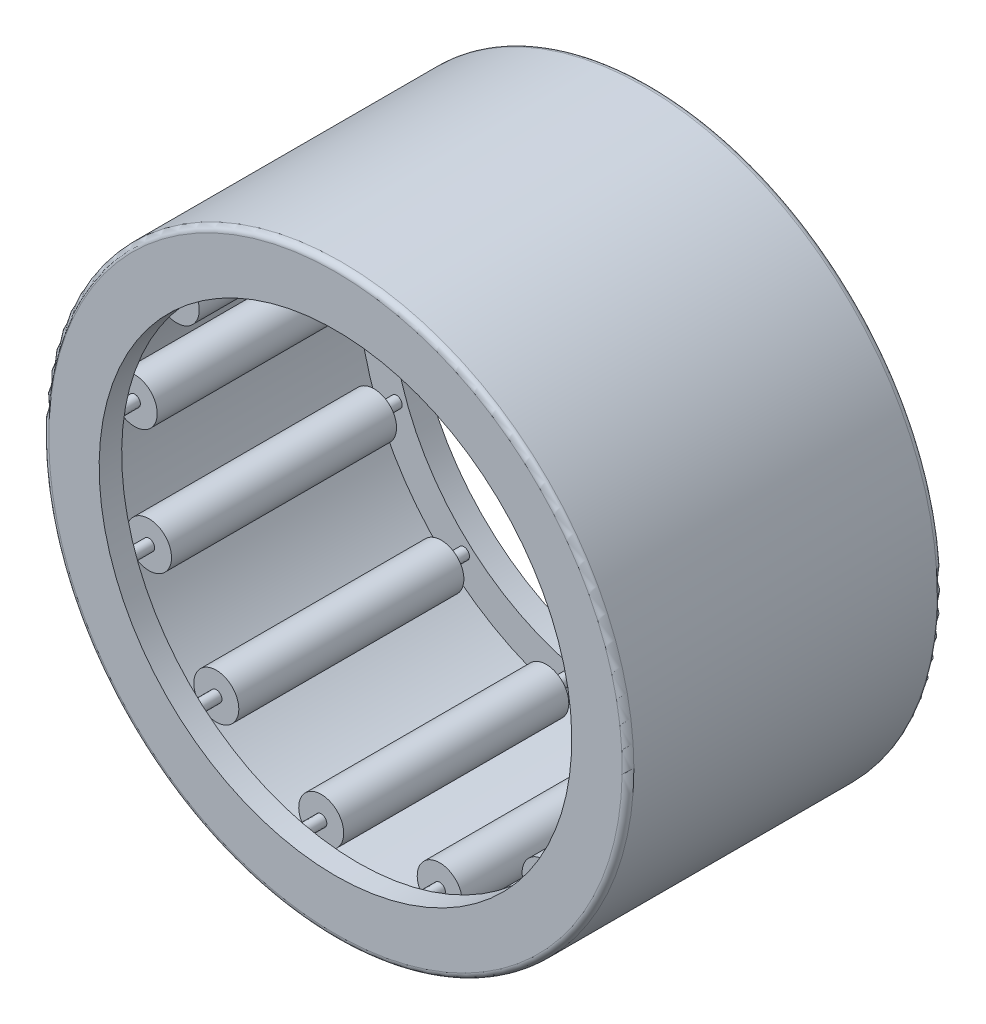
SolidWorks part; units mm, degrees
ref_plane "Front Plane" through (0, 0, 0) normal (0, 0, 1) x (1, 0, 0)
ref_plane "Top Plane" through (0, 0, 0) normal (0, 1, 0) x (1, 0, 0)
ref_plane "Right Plane" through (0, 0, 0) normal (1, 0, 0) x (0, 0, -1)
sketch "Sketch1" plane through (0, 0, 0) normal (1, 0, 0) x (0, 0, -1)
  line L0 (-5.5563, 0) -> (5.5562, 0) construction
  line L1 (0, 0) -> (0, 10.3187) construction
  line L2 (-5.5563, 0) -> (-5.5563, 10.3187) construction
  line L3 (-5.5563, 10.3187) -> (5.5563, 10.3187)
  line L4 (5.5563, 10.3187) -> (5.5562, 0) construction
  line L5 (5.5562, 0) -> (4.7625, 0) construction
  line L6 (4.7625, 0) -> (4.7625, 9.525) construction
  line L7 (4.7625, 9.525) -> (-4.7625, 9.525)
  line L8 (-4.7625, 9.525) -> (-4.7625, 0) construction
  line L9 (-4.7625, 0) -> (-5.5563, 0) construction
  line L10 (-5.5563, 10.3187) -> (-5.5563, 8.3344)
  line L11 (-5.5563, 8.3344) -> (-4.7625, 8.3344)
  line L12 (-4.7625, 8.3344) -> (-4.7625, 9.525)
  line L13 (4.7625, 10.3187) -> (4.7625, 9.525) construction
  line L14 (4.7625, 9.525) -> (4.7625, 8.3344)
  line L15 (4.7625, 8.3344) -> (5.5563, 8.3344)
  line L16 (5.5563, 8.3344) -> (5.5563, 10.3187)
  line L17 (4.7625, 9.525) -> (4.7625, 8.7312) construction
  line L18 (4.7625, 8.7312) -> (4.7625, 7.9375) construction
  point P5 (0, 7.9375)
  dimension "Width" = 11.1125
  dimension "OD" = 20.6375
  dimension "Shaft Dia" = 15.875
revolve "Revolve1" add sketch "Sketch1" angle 360 about L0
sketch "Sketch2" plane through (0, 0, 0) normal (1, 0, 0) x (0, 0, -1)
  line L0 (4.7625, 9.525) -> (-4.7625, 9.525) construction
  line L1 (-3.9687, 8.7312) -> (3.9687, 8.7313) construction
  line L2 (-3.9687, 8.7312) -> (-3.9687, 9.525) construction
  line L3 (-3.9687, 9.525) -> (3.9687, 9.525)
  line L4 (3.9687, 8.7313) -> (3.9687, 9.525) construction
  line L5 (4.7625, 8.3344) -> (5.5563, 8.3344) construction
  line L6 (-4.7625, 8.7312) -> (-3.9687, 8.7312) construction
  line L7 (3.9687, 8.7313) -> (4.7625, 8.7313) construction
  line L8 (-5.5563, 8.3344) -> (-4.7625, 8.3344) construction
  line L9 (-3.9687, 8.9297) -> (-3.9687, 8.5328) construction
  line L10 (-4.7625, 8.7312) -> (-4.7625, 8.3344) construction
  line L11 (-3.9687, 9.525) -> (-3.9687, 8.9297)
  line L12 (3.9687, 9.525) -> (3.9687, 8.9297)
  line L13 (3.9687, 8.9297) -> (-3.9687, 8.9297)
  line L14 (0, 9.525) -> (0, 7.9375) construction
  line L15 (-4.7625, 8.3344) -> (-4.7625, 9.525) construction
  line L16 (-3.9687, 8.5328) -> (-4.7625, 8.5328) construction
  line L17 (0, 0) -> (5.5563, 0) construction
  line L31 (5.5563, -10.3188) -> (5.5562, 10.3187) construction
  point P16 (0, 8.7312)
revolve "Revolve2" add sketch "Sketch2" angle 360 about L1
sketch "Sketch3" plane through (0, 0, 0) normal (1, 0, 0) x (0, 0, -1)
  line L0 (4.7625, 9.525) -> (4.7625, 8.3344) construction
  line L1 (-4.7625, 8.7312) -> (4.7625, 8.7312)
  line L2 (-4.7625, 8.7312) -> (-4.7625, 8.9297)
  line L3 (-4.7625, 8.9297) -> (4.7625, 8.9297)
  line L4 (4.7625, 8.7312) -> (4.7625, 8.9297)
  line L5 (0, 0) -> (5.5563, 0) construction
  line L6 (5.5563, -10.3188) -> (5.5562, 10.3187) construction
revolve "Revolve3" add sketch "Sketch3" angle 360 about L1
ref_axis "Axis1" through (0, 0, -5.5562) along (0, 0, 1)
pattern_circular "CirPattern1" count 13 every 27.692 about axis through (0, 0, -5.5562) along (0, 0, 1) of bodies 166 167
fillet "Fillet1" radius 0.2064 2 edges at (0, -10.3188, -5.5563) (0, -10.3188, 5.5562)
sketch "Sketch4" plane through (0, 0, 0) normal (1, 0, 0) x (0, 0, -1)
  line L1 (5.3499, 7.9375) -> (3.9687, 7.9375)
  line L2 (5.3499, 7.9375) -> (5.3499, 8.3344)
  line L3 (5.3499, 8.3344) -> (3.9687, 8.3344)
  line L4 (3.9687, 7.9375) -> (3.9687, 8.3344)
  line L5 (-5.5563, 8.3344) -> (-4.7625, 8.3344) construction
  line L6 (5.3499, -10.3188) -> (5.3499, 10.3187) construction
  line L7 (3.9687, 9.525) -> (3.9687, 8.9297) construction
revolve "Revolve4" [suppressed] add sketch "Sketch4" angle 360 about L0
sketch "Sketch5" plane through (0, 0, 0) normal (1, 0, 0) x (0, 0, -1)
  line L0 (-5.3499, 10.3187) -> (-5.3499, -10.3188) construction
  line L1 (-3.9687, 7.9375) -> (-5.3499, 7.9375)
  line L2 (-3.9687, 7.9375) -> (-3.9687, 8.3344)
  line L3 (-3.9687, 8.3344) -> (-5.3499, 8.3344)
  line L4 (-5.3499, 7.9375) -> (-5.3499, 8.3344)
  line L6 (-3.9687, 9.525) -> (-3.9687, 8.9297) construction
  line L7 (-5.5563, 8.3344) -> (-4.7625, 8.3344) construction
revolve "Revolve5" [suppressed] add sketch "Sketch5" angle 360 about L0
sketch "Front View" plane through (0, 0, 0) normal (0, 0, 1) x (1, 0, 0)
  circle A0 centre (0, 0) radius 7.9375 construction
  circle A1 centre (0, 0) radius 10.3187 construction
  dimension "OD" = 20.6375
  dimension "ID" = 15.875
sketch "Right View" plane through (0, 0, 0) normal (1, 0, 0) x (0, 0, -1)
  line L0 (-5.5562, 10.3187) -> (5.5562, 10.3187) construction
  dimension "Width" = 11.1125
ref_axis "Center Axis 1" through (0, 0, -5.3499) along (0, 0, 1)
ref_plane "Contact Plane 1" through (0, 0, 5.5562) normal (0, 0, 1) x (1, 0, 0)
ref_plane "Contact Plane 2" through (0, 0, -5.5563) normal (0, 0, -1) x (-1, 0, 0)
equation "\"Rollers@CirPattern1\" = \"OD@Sketch1\"*16"
equation "\"D1@Fillet1\" = \"OD@Sketch1\"*.01"
equation "\"Angle@CirPattern1\"= 360 / \"Rollers@CirPattern1\""
equation "\"OD@Front View\"=\"OD@Sketch1\""
equation "\"ID@Front View\"=\"Shaft Dia@Sketch1\""
equation "\"Width@Right View\"=\"Width@Sketch1\""
